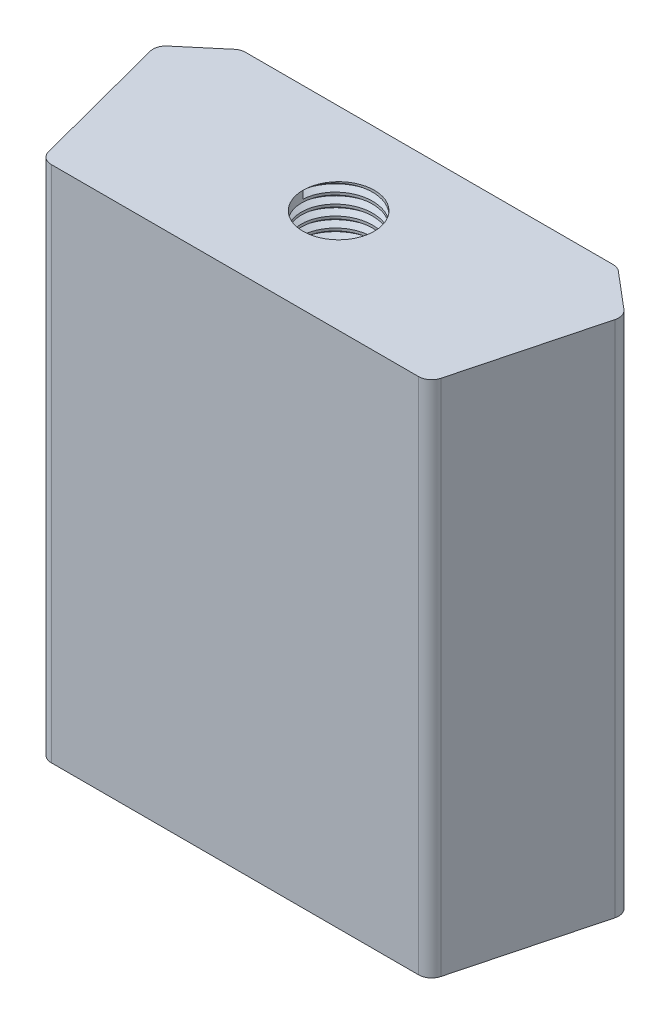
SolidWorks part; units mm, degrees
ref_plane "Front Plane" through (0, 0, 0) normal (0, 0, 1) x (1, 0, 0)
ref_plane "Top Plane" through (0, 0, 0) normal (0, 1, 0) x (1, 0, 0)
ref_plane "Right Plane" through (0, 0, 0) normal (1, 0, 0) x (0, 0, -1)
sketch "Sketch1" plane through (0, 0, 0) normal (0, 1, 0) x (1, 0, 0)
  line L0 (0, 0) -> (0, -50000) construction
  line L1 (0, 0) -> (50000, 0) construction
  line L2 (-14.1786, -8) -> (14.1786, -8)
  line L8 (-15.1459, -7.2539) -> (-17.9398, 3.3896)
  line L9 (-17.618, 4.4073) -> (-14.8295, 6.7638)
  line L10 (15.1459, -7.2539) -> (17.9398, 3.3896)
  line L11 (17.618, 4.4073) -> (14.8295, 6.7638)
  line L16 (-14.1841, 7) -> (14.1841, 7)
  arc A0 (-14.1786, -8) -> (-15.1459, -7.2539) centre (-14.1786, -7) cw
  arc A1 (-17.9398, 3.3896) -> (-17.618, 4.4073) centre (-16.9725, 3.6435) cw
  arc A2 (-14.8295, 6.7638) -> (-14.1841, 7) centre (-14.1841, 6) cw
  arc A3 (14.1841, 7) -> (14.8295, 6.7638) centre (14.1841, 6) cw
  arc A4 (17.618, 4.4073) -> (17.9398, 3.3896) centre (16.9725, 3.6435) cw
  arc A5 (14.1786, -8) -> (15.1459, -7.2539) centre (14.1786, -7) ccw
  dimension "D4" = 1
  dimension "D5" = 1
  dimension "D6" = 1
  dimension "D7" = 1
  dimension "D8" = 1
  dimension "D9" = 1
  dimension "D10" = 10.6435
  dimension "D11" = 10.6435
  dimension "D15" = 2.7939
  dimension "D3" = 28.3681
  dimension "D12" = 2.3565
  dimension "D13" = 2.3565
  dimension "D14" = 2.7885
  dimension "D22" = 35.8796
extrude "Boss-Extrude1" add sketch "Sketch1" along normal blind 40
sketch "Sketch3" plane through (0, 40, 0) normal (0, 1, 0) x (1, 0, 0)
  circle A0 centre (0, 0) radius 2.75
  dimension "D1" = 5.5
extrude "Cut-Extrude1" cut sketch "Sketch3" against normal blind 10
thread "Thread1" pitch 0.8 method cut profile "Thread Profile1" start angle 0, offset 0, length 10, pitch 0.8, diameter 5.5
ref_plane "Plane1" through (-2.75, 40, 0) normal (0, 0, 1) x (-1, 0, 0)
sketch "Thread Profile1" plane through (-2.75, 40, 0) normal (0, 0, 1) x (-1, 0, 0)
  line L0 (0, 0) -> (0, 0.8) construction
  line L1 (0, 0) -> (0.433, 0.25)
  line L2 (0.433, 0.25) -> (0.433, 0.35)
  line L3 (0.433, 0.35) -> (0, 0.6)
  line L4 (0.433, 0.3) -> (0, 0.3) construction
  line L11 (0, 0) -> (0, 0.6)
  point P2 (0, 0)
  dimension "Pitch" = 0.8
  dimension "Profile_Angle" = 60
  dimension "Profile_Land" = 0.1
  dimension "Profile_Height" = 0.433
